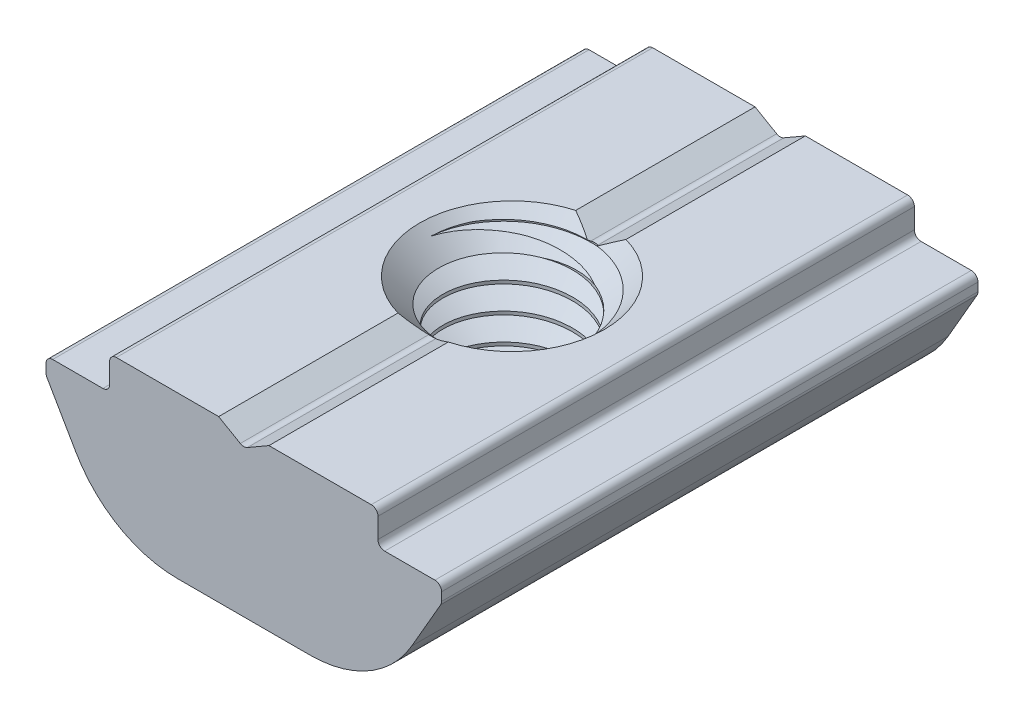
SolidWorks part; units mm, degrees
ref_plane "Front Plane" through (0, 0, 0) normal (0, 0, 1) x (1, 0, 0)
ref_plane "Top Plane" through (0, 0, 0) normal (0, 1, 0) x (1, 0, 0)
ref_plane "Right Plane" through (0, 0, 0) normal (1, 0, 0) x (0, 0, -1)
sketch "Sketch1" plane through (0, 0, 0) normal (0, 0, 1) x (1, 0, 0)
  line L0 (0, -2.4) -> (0, 2.4) construction
  line L1 (-4.002, 2.4) -> (4.002, 2.4) construction
  line L2 (-5.9, -2.4) -> (5.9, -2.4) construction
  line L3 (-4.002, 2.4) -> (-4.002, 1.4) construction
  point P4 (0, 0)
  dimension "Top Width" = 8.004
  dimension "Width" = 11.8
  dimension "Thickness" = 4.8
  dimension "Step Height" = 1
sketch "Sketch2" plane through (0, 0, 0) normal (0, 1, 0) x (1, 0, 0)
  line L0 (0, 8) -> (0, -8) construction
  line L1 (0, 0) -> (-0.8, 0) construction
  line L2 (-5.9, 0) -> (5.9, 0) construction
  line L3 (0, 0) -> (2.1651, -1.25) construction
  circle A0 centre (0, 0) radius 2.5 construction
  point P11 (2.1651, -1.25)
  dimension "Thread Size" = 5
  dimension "Length" = 16
  dimension "Thread Pitch" = 0.8
  dimension "D1" = 30
  dimension "Hole Offset" = 8
sketch "Sketch3" plane through (0, 0, 0) normal (0, 0, 1) x (1, 0, 0)
  line L0 (0, 2.4) -> (0, -2.4) construction
  line L1 (-4.002, 2.4) -> (4.002, 2.4) construction
  line L2 (-5.9, -2.4) -> (5.9, -2.4) construction
  line L3 (3.802, 2.4) -> (0.75, 2.4)
  line L4 (-4.002, 2.2) -> (-4.002, 1.6)
  line L5 (-4.202, 1.4) -> (-5.7, 1.4)
  line L6 (-5.9, 1.2) -> (-5.9, 0.95)
  line L7 (-5.8732, 0.85) -> (-5.0072, -0.65)
  line L8 (-1.9761, -2.4) -> (1.9761, -2.4)
  line L9 (5.8732, 0.85) -> (5.0072, -0.65)
  line L10 (5.9, 1.2) -> (5.9, 0.95)
  line L11 (4.202, 1.4) -> (5.7, 1.4)
  line L12 (4.002, 2.2) -> (4.002, 1.6)
  line L13 (-0.75, 2.4) -> (-0.105, 2.0276)
  line L14 (0.105, 2.0276) -> (0.75, 2.4)
  line L15 (-0.75, 2.4) -> (-3.802, 2.4)
  arc A0 (5.9, 1.2) -> (5.7, 1.4) centre (5.7, 1.2) ccw
  arc A1 (4.002, 2.2) -> (3.802, 2.4) centre (3.802, 2.2) ccw
  arc A2 (-3.802, 2.4) -> (-4.002, 2.2) centre (-3.802, 2.2) ccw
  arc A3 (-5.7, 1.4) -> (-5.9, 1.2) centre (-5.7, 1.2) ccw
  arc A4 (5.0072, -0.65) -> (1.9761, -2.4) centre (1.9761, 1.1) cw
  arc A5 (-5.0072, -0.65) -> (-1.9761, -2.4) centre (-1.9761, 1.1) ccw
  arc A6 (-5.9, 0.95) -> (-5.8732, 0.85) centre (-5.7, 0.95) ccw
  arc A7 (5.8732, 0.85) -> (5.9, 0.95) centre (5.7, 0.95) ccw
  arc A8 (4.202, 1.4) -> (4.002, 1.6) centre (4.202, 1.6) cw
  arc A9 (-4.002, 1.6) -> (-4.202, 1.4) centre (-4.202, 1.6) cw
  arc A10 (-0.105, 2.0276) -> (0.105, 2.0276) centre (0, 2.2095) ccw
  point P21 (5.9, 1.4)
  point P24 (4.002, 2.4)
  point P27 (-4.002, 2.4)
  point P30 (-5.9, 1.4)
  point P33 (3.9968, -2.4)
  point P36 (-3.9968, -2.4)
  point P41 (-5.9, 0.8964)
  point P44 (5.9, 0.8964)
  point P46 (0, 1.967)
  point P50 (4.002, 1.4)
  point P53 (-4.002, 1.4)
  dimension "D3" = 0.2
  dimension "D2" = 3.5
  dimension "D4" = 0.25
  dimension "D5" = 0.21
  dimension "D1" = 60
  dimension "D6" = 120
  dimension "D7" = 1.5
extrude "Boss-Extrude1" add sketch "Sketch3" along normal up to vertex (8 mm away) and the other way up to vertex (8 mm away) up to point (0, 0, 8) other way up to point (0, 0, -8)
sketch "Sketch4" plane through (0, 2.4, 0) normal (0, 1, 0) x (1, 0, 0)
  circle A0 centre (0, 0) radius 2.5 construction
  circle A1 centre (0, 0) radius 2.5
extrude "Cut-Extrude1" cut sketch "Sketch4" against normal through all
sketch "Sketch5" plane through (0, 2.4, 0) normal (0, 1, 0) x (1, 0, 0)
  circle A0 centre (0, 0) radius 2.5 construction
  circle A1 centre (0, 0) radius 2.5 construction
  circle A2 centre (0, 0) radius 2.754
  dimension "D1" = 0.254
extrude "Cut-Extrude2" cut sketch "Sketch5" against normal through all draft 45
sketch "Sketch6" plane through (0, -2.4, 0) normal (0, -1, 0) x (1, 0, 0)
  circle A0 centre (0, 0) radius 2.5 construction
  circle A1 centre (0, 0) radius 2.5 construction
  circle A2 centre (0, 0) radius 3.135
  dimension "D1" = 0.635
extrude "Cut-Extrude3" cut sketch "Sketch6" against normal through all draft 45
sketch "Sketch7" plane through (0, 2.4, 0) normal (0, 1, 0) x (1, 0, 0)
  circle A0 centre (0, 0) radius 2.5 construction
  circle A1 centre (0, 0) radius 2.5
curve "Helix/Spiral1" pitch 0.8 height 5.6 radius 2.5 centre (0, 2.4, 0) axis (0, -1, 0) start towards (0, 0, 1)
sketch "Sketch8" plane through (0, 0, 0) normal (1, 0, 0) x (0, 0, -1)
  line L0 (-2.5433, 2.375) -> (-1.8505, 2.775) construction
  line L1 (-1.8505, 2.775) -> (-2.5433, 3.175) construction
  line L2 (-2.5433, 3.175) -> (-2.5433, 2.375) construction
  line L3 (-2.4567, 2.425) -> (-2.4567, 3.125) construction
  line L4 (-2.5433, 2.775) -> (-2.4567, 2.775) construction
  line L5 (-2.4567, 2.775) -> (-1.9371, 2.775) construction
  line L6 (-1.9371, 2.775) -> (-1.8505, 2.775) construction
  line L7 (-1.9371, 2.725) -> (-1.9371, 2.825)
  line L8 (-2.5, 2.4) -> (-2.5, 3.15)
  line L9 (-1.9371, 2.825) -> (-2.5, 3.15)
  line L10 (-1.9371, 2.725) -> (-2.5, 2.4)
  line L12 (2.5, 2.4) -> (-2.5, 2.4) construction
  line L13 (2.5, 2.4) -> (-2.5, 2.4) construction
  point P12 (-2.5, 2.775)
  dimension "D1" = 0.8
  dimension "D2" = 0.1
sweep "Sweep1" add profiles "Sketch8" path "Helix/Spiral1"
sketch "Sketch9" plane through (0, 2.4, 0) normal (0, 1, 0) x (1, 0, 0)
  circle A0 centre (0, 0) radius 2.754 construction
  circle A1 centre (0, 0) radius 2.754
extrude "Cut-Extrude4" cut sketch "Sketch9" against normal through all draft 45 and the other way through all
sketch "Sketch10" plane through (0, -2.4, 0) normal (0, -1, 0) x (1, 0, 0)
  circle A1 centre (0, 0) radius 3.135
  circle A2 centre (0, 0) radius 3.135 construction
extrude "Cut-Extrude5" cut sketch "Sketch10" against normal through all draft 45 and the other way through all
sketch "Sketch11" plane through (0, 0, 8) normal (0, 0, 1) x (1, 0, 0)
  line L0 (0.75, 2.4) -> (0.105, 2.0276) construction
  line L1 (-0.105, 2.0276) -> (-0.75, 2.4) construction
  line L2 (0.75, 2.4) -> (0.105, 2.0276)
  line L3 (-0.105, 2.0276) -> (-0.75, 2.4)
  line L4 (-0.75, 2.4) -> (0.75, 2.4)
  arc A0 (-0.105, 2.0276) -> (0.105, 2.0276) centre (0, 2.2095) ccw construction
  arc A1 (-0.105, 2.0276) -> (0.105, 2.0276) centre (0, 2.2095) ccw
extrude "Cut-Extrude6" cut sketch "Sketch11" against normal through all
equation "\"D4@Helix/Spiral1\"=\"Thread Pitch@Sketch2\""
equation "\"D3@Helix/Spiral1\"=\"Thickness@Sketch1\" + \"Thread Pitch@Sketch2\""
equation "\"D2@Sketch8\" = \"D1@Sketch8\" / 8"
equation "\"D1@Sketch8\" = \"Thread Pitch@Sketch2\""
